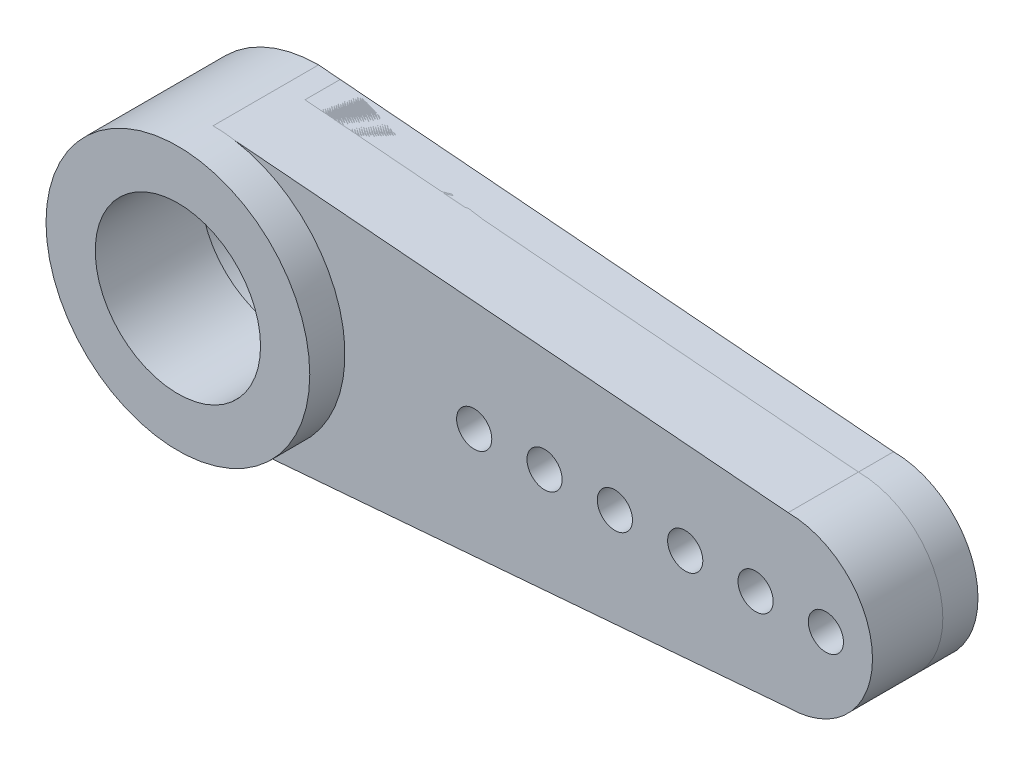
SolidWorks part; units mm, degrees
ref_plane "Front Plane" through (0, 0, 0) normal (0, 0, 1) x (1, 0, 0)
ref_plane "Top Plane" through (0, 0, 0) normal (0, 1, 0) x (1, 0, 0)
ref_plane "Right Plane" through (0, 0, 0) normal (1, 0, 0) x (0, 0, -1)
sketch "Sketch1" plane through (0, 0, 0) normal (0, 0, 1) x (1, 0, 0)
  line L0 (-6.5926, 3.75) -> (9.7574, 2.4)
  line L1 (-6.5926, -3.75) -> (9.7574, -2.4)
  arc A0 (-5.9775, 3.6992) -> (-5.9775, -3.6992) centre (-6.5926, 0) ccw
  arc A1 (9.7574, -2.4) -> (9.7574, 2.4) centre (9.7574, 0) ccw
  circle A2 centre (-6.5926, 0) radius 2.35
  dimension "D1" = 7.5
  dimension "D2" = 4.8
  dimension "D4" = 4.7
  dimension "D3" = 16.35
extrude "Boss-Extrude1" add sketch "Sketch1" along normal blind 2 contours L1 A1 L0 A0 A2 region at (1.1375, 0, 0)
sketch "Sketch2" plane through (0, 0, 2) normal (0, 0, 1) x (1, 0, 0)
  line L2 (-6.5926, -3.75) -> (9.7574, -2.4)
  line L3 (9.7574, 2.4) -> (-6.5926, 3.75)
  circle A0 centre (-6.5926, 0) radius 2.35 construction
  circle A1 centre (-6.5926, 0) radius 2.35
  arc A2 (9.7574, -2.4) -> (9.7574, 2.4) centre (9.7574, 0) ccw
  arc A3 (-6.5926, 3.75) -> (-6.5926, -3.75) centre (-6.5926, 0) ccw
  arc A5 (-6.5926, 3.75) -> (-6.5926, -3.75) centre (-6.5926, 0) ccw
  arc A6 (-6.5926, 3.75) -> (-6.5926, -3.75) centre (-6.5926, 0) cw
  dimension "D1" = 0
extrude "Boss-Extrude2" add sketch "Sketch2" along normal blind 1
sketch "Sketch3" plane through (0, 0, 0) normal (0, 0, -1) x (-1, 0, 0)
  line L2 (-9.7574, -2.4) -> (6.5926, -3.75)
  line L3 (6.5926, 3.75) -> (-9.7574, 2.4)
  circle A0 centre (6.5926, 0) radius 2.35 construction
  circle A1 centre (6.5926, 0) radius 2.35
  arc A2 (6.5926, -3.75) -> (6.5926, 3.75) centre (6.5926, 0) ccw
  arc A3 (-9.7574, 2.4) -> (-9.7574, -2.4) centre (-9.7574, 0) ccw
  arc A4 (6.5926, -3.75) -> (6.5926, 3.75) centre (6.5926, 0) ccw
  circle A6 centre (6.5926, 0) radius 2.75
  arc A7 (6.5926, 3.75) -> (6.5926, -3.75) centre (6.5926, 0) ccw
  line M6 (-9.7574, -2.4) -> (6.5926, -3.75)
  arc M7 (6.5926, -3.75) -> (6.5926, 3.75) centre (6.5926, 0) ccw
  line M8 (6.5926, 3.75) -> (-9.7574, 2.4)
  dimension "D2" = 5.5
  dimension "D1" = 0
extrude "Boss-Extrude3" add sketch "Sketch3" along normal blind 1 contours A7 A6 M8 M6 M7 region at (-2.9486, 0, 0)
fillet "Fillet1" radius 5 1 edges at (-2.8426, 0, 0)
sketch "Sketch4" plane through (0, 0, 0) normal (0, 0, -1) x (-1, 0, 0)
  circle A0 centre (-10.8328, 0) radius 0.5
  circle A1 centre (-8.8328, 0) radius 0.5
  circle A2 centre (-6.8328, 0) radius 0.5
  circle A3 centre (-4.8328, 0) radius 0.5
  circle A4 centre (-2.8328, 0) radius 0.5
  circle A5 centre (-0.8328, 0) radius 0.5
  dimension "D1" = 1
  dimension "D2" = 6
extrude "Cut-Extrude1" cut sketch "Sketch4" against normal up to next
sketch "Sketch5" plane through (0, 0, 0) normal (0, 0, -1) x (-1, 0, 0)
  line L0 (5.9775, 3.6992) -> (0.6831, 3.2621) construction
  line L1 (0.6831, -3.2621) -> (5.9775, -3.6992) construction
  line L2 (-9.7574, -2.4) -> (0.6831, -3.2621) construction
  line L3 (0.6831, 3.2621) -> (-9.7574, 2.4) construction
  line L4 (5.9775, 3.6992) -> (0.6831, 3.2621)
  line L5 (0.6831, -3.2621) -> (5.9775, -3.6992)
  line L6 (-9.7574, -2.4) -> (0.6831, -3.2621)
  line L7 (0.6831, 3.2621) -> (-9.7574, 2.4)
  arc A0 (5.9775, 3.6992) -> (5.9775, -3.6992) centre (6.5926, 0) ccw construction
  arc A1 (-9.7574, 2.4) -> (-9.7574, -2.4) centre (-9.7574, 0) ccw construction
  arc A2 (5.9775, 3.6992) -> (5.9775, -3.6992) centre (6.5926, 0) ccw
  arc A3 (-9.7574, 2.4) -> (-9.7574, -2.4) centre (-9.7574, 0) ccw
  circle A4 centre (-10.8328, 0) radius 0.5 construction
  circle A5 centre (-8.8328, 0) radius 0.5 construction
  circle A6 centre (-6.8328, 0) radius 0.5 construction
  circle A7 centre (-4.8328, 0) radius 0.5 construction
  circle A8 centre (-2.8328, 0) radius 0.5 construction
  circle A9 centre (-0.8328, 0) radius 0.5 construction
  circle A10 centre (-10.8328, 0) radius 0.5
  circle A11 centre (-8.8328, 0) radius 0.5
  circle A12 centre (-6.8328, 0) radius 0.5
  circle A13 centre (-4.8328, 0) radius 0.5
  circle A14 centre (-2.8328, 0) radius 0.5
  circle A15 centre (-0.8328, 0) radius 0.5
extrude "Boss-Extrude4" add sketch "Sketch5" along normal up to surface (1 mm away) separate body up to face at (-9.3426, 0, -1)
